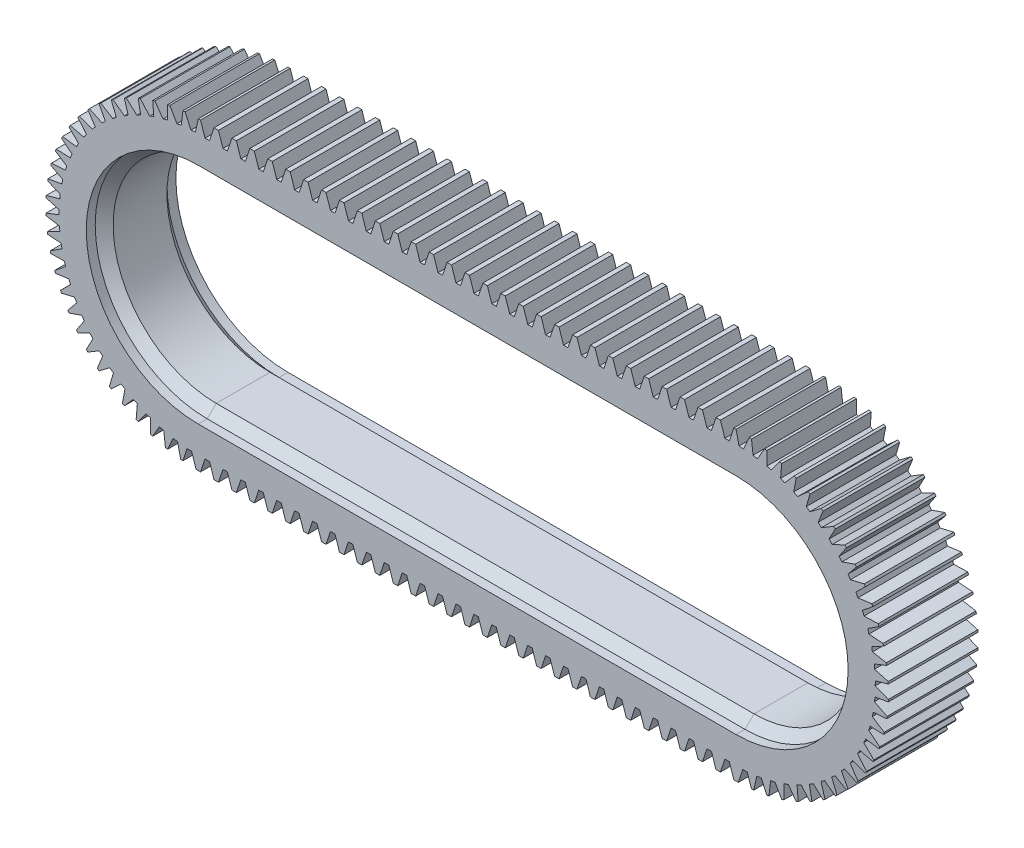
SolidWorks part; units mm, degrees
ref_plane "Ön Düzlem" through (0, 0, 0) normal (0, 0, 1) x (1, 0, 0)
ref_plane "Üst Düzlem" through (0, 0, 0) normal (0, 1, 0) x (1, 0, 0)
ref_plane "Sağ Düzlem" through (0, 0, 0) normal (1, 0, 0) x (0, 0, -1)
sketch "Çizim1" plane through (0, 0, 0) normal (0, 0, 1) x (1, 0, 0)
  line L0 (-26.25, 17) -> (-26, 17)
  line L3 (-30, 0) -> (30, 0) construction
  line L4 (-30, 12.5) -> (30, 12.5)
  line L5 (-30, -12.5) -> (30, -12.5)
  line L6 (-29.999, 17) -> (-29.75, 17)
  line L7 (-29.75, 17) -> (-29.25, 15.5)
  line L8 (-29.25, 15.5) -> (-28.75, 15.5)
  line L9 (-28.75, 15.5) -> (-28.25, 17)
  line L10 (-28.25, 17) -> (-28, 17)
  line L11 (-26.75, 15.5) -> (-26.25, 17)
  line L12 (-27.25, 15.5) -> (-26.75, 15.5)
  line L13 (-27.75, 17) -> (-27.25, 15.5)
  line L14 (-28, 17) -> (-27.75, 17)
  line L15 (-24.25, 17) -> (-24, 17)
  line L16 (-24.75, 15.5) -> (-24.25, 17)
  line L17 (-25.25, 15.5) -> (-24.75, 15.5)
  line L18 (-25.75, 17) -> (-25.25, 15.5)
  line L19 (-26, 17) -> (-25.75, 17)
  line L20 (-22.25, 17) -> (-22, 17)
  line L21 (-22.75, 15.5) -> (-22.25, 17)
  line L22 (-23.25, 15.5) -> (-22.75, 15.5)
  line L23 (-23.75, 17) -> (-23.25, 15.5)
  line L24 (-24, 17) -> (-23.75, 17)
  line L25 (-20.25, 17) -> (-20, 17)
  line L26 (-20.75, 15.5) -> (-20.25, 17)
  line L27 (-21.25, 15.5) -> (-20.75, 15.5)
  line L28 (-21.75, 17) -> (-21.25, 15.5)
  line L29 (-22, 17) -> (-21.75, 17)
  line L30 (-18.25, 17) -> (-18, 17)
  line L31 (-18.75, 15.5) -> (-18.25, 17)
  line L32 (-19.25, 15.5) -> (-18.75, 15.5)
  line L33 (-19.75, 17) -> (-19.25, 15.5)
  line L34 (-20, 17) -> (-19.75, 17)
  line L35 (-16.25, 17) -> (-16, 17)
  line L36 (-16.75, 15.5) -> (-16.25, 17)
  line L37 (-17.25, 15.5) -> (-16.75, 15.5)
  line L38 (-17.75, 17) -> (-17.25, 15.5)
  line L39 (-18, 17) -> (-17.75, 17)
  line L40 (-14.25, 17) -> (-14, 17)
  line L41 (-14.75, 15.5) -> (-14.25, 17)
  line L42 (-15.25, 15.5) -> (-14.75, 15.5)
  line L43 (-15.75, 17) -> (-15.25, 15.5)
  line L44 (-16, 17) -> (-15.75, 17)
  line L45 (-12.25, 17) -> (-12, 17)
  line L46 (-12.75, 15.5) -> (-12.25, 17)
  line L47 (-13.25, 15.5) -> (-12.75, 15.5)
  line L48 (-13.75, 17) -> (-13.25, 15.5)
  line L49 (-14, 17) -> (-13.75, 17)
  line L50 (-10.25, 17) -> (-10, 17)
  line L51 (-10.75, 15.5) -> (-10.25, 17)
  line L52 (-11.25, 15.5) -> (-10.75, 15.5)
  line L53 (-11.75, 17) -> (-11.25, 15.5)
  line L54 (-12, 17) -> (-11.75, 17)
  line L55 (-8.25, 17) -> (-8, 17)
  line L56 (-8.75, 15.5) -> (-8.25, 17)
  line L57 (-9.25, 15.5) -> (-8.75, 15.5)
  line L58 (-9.75, 17) -> (-9.25, 15.5)
  line L59 (-10, 17) -> (-9.75, 17)
  line L60 (-6.25, 17) -> (-6, 17)
  line L61 (-6.75, 15.5) -> (-6.25, 17)
  line L62 (-7.25, 15.5) -> (-6.75, 15.5)
  line L63 (-7.75, 17) -> (-7.25, 15.5)
  line L64 (-8, 17) -> (-7.75, 17)
  line L65 (-4.25, 17) -> (-4, 17)
  line L66 (-4.75, 15.5) -> (-4.25, 17)
  line L67 (-5.25, 15.5) -> (-4.75, 15.5)
  line L68 (-5.75, 17) -> (-5.25, 15.5)
  line L69 (-6, 17) -> (-5.75, 17)
  line L70 (-2.25, 17) -> (-2, 17)
  line L71 (-2.75, 15.5) -> (-2.25, 17)
  line L72 (-3.25, 15.5) -> (-2.75, 15.5)
  line L73 (-3.75, 17) -> (-3.25, 15.5)
  line L74 (-4, 17) -> (-3.75, 17)
  line L75 (-0.25, 17) -> (0, 17)
  line L76 (-0.75, 15.5) -> (-0.25, 17)
  line L77 (-1.25, 15.5) -> (-0.75, 15.5)
  line L78 (-1.75, 17) -> (-1.25, 15.5)
  line L79 (-2, 17) -> (-1.75, 17)
  line L80 (1.75, 17) -> (2, 17)
  line L81 (1.25, 15.5) -> (1.75, 17)
  line L82 (0.75, 15.5) -> (1.25, 15.5)
  line L83 (0.25, 17) -> (0.75, 15.5)
  line L84 (0, 17) -> (0.25, 17)
  line L85 (3.75, 17) -> (4, 17)
  line L86 (3.25, 15.5) -> (3.75, 17)
  line L87 (2.75, 15.5) -> (3.25, 15.5)
  line L88 (2.25, 17) -> (2.75, 15.5)
  line L89 (2, 17) -> (2.25, 17)
  line L90 (5.75, 17) -> (6, 17)
  line L91 (5.25, 15.5) -> (5.75, 17)
  line L92 (4.75, 15.5) -> (5.25, 15.5)
  line L93 (4.25, 17) -> (4.75, 15.5)
  line L94 (4, 17) -> (4.25, 17)
  line L95 (7.75, 17) -> (8, 17)
  line L96 (7.25, 15.5) -> (7.75, 17)
  line L97 (6.75, 15.5) -> (7.25, 15.5)
  line L98 (6.25, 17) -> (6.75, 15.5)
  line L99 (6, 17) -> (6.25, 17)
  line L100 (9.75, 17) -> (10, 17)
  line L101 (9.25, 15.5) -> (9.75, 17)
  line L102 (8.75, 15.5) -> (9.25, 15.5)
  line L103 (8.25, 17) -> (8.75, 15.5)
  line L104 (8, 17) -> (8.25, 17)
  line L105 (11.75, 17) -> (12, 17)
  line L106 (11.25, 15.5) -> (11.75, 17)
  line L107 (10.75, 15.5) -> (11.25, 15.5)
  line L108 (10.25, 17) -> (10.75, 15.5)
  line L109 (10, 17) -> (10.25, 17)
  line L110 (13.75, 17) -> (14, 17)
  line L111 (13.25, 15.5) -> (13.75, 17)
  line L112 (12.75, 15.5) -> (13.25, 15.5)
  line L113 (12.25, 17) -> (12.75, 15.5)
  line L114 (12, 17) -> (12.25, 17)
  line L115 (15.75, 17) -> (16, 17)
  line L116 (15.25, 15.5) -> (15.75, 17)
  line L117 (14.75, 15.5) -> (15.25, 15.5)
  line L118 (14.25, 17) -> (14.75, 15.5)
  line L119 (14, 17) -> (14.25, 17)
  line L120 (17.75, 17) -> (18, 17)
  line L121 (17.25, 15.5) -> (17.75, 17)
  line L122 (16.75, 15.5) -> (17.25, 15.5)
  line L123 (16.25, 17) -> (16.75, 15.5)
  line L124 (16, 17) -> (16.25, 17)
  line L125 (19.75, 17) -> (20, 17)
  line L126 (19.25, 15.5) -> (19.75, 17)
  line L127 (18.75, 15.5) -> (19.25, 15.5)
  line L128 (18.25, 17) -> (18.75, 15.5)
  line L129 (18, 17) -> (18.25, 17)
  line L130 (21.75, 17) -> (22, 17)
  line L131 (21.25, 15.5) -> (21.75, 17)
  line L132 (20.75, 15.5) -> (21.25, 15.5)
  line L133 (20.25, 17) -> (20.75, 15.5)
  line L134 (20, 17) -> (20.25, 17)
  line L135 (23.75, 17) -> (24, 17)
  line L136 (23.25, 15.5) -> (23.75, 17)
  line L137 (22.75, 15.5) -> (23.25, 15.5)
  line L138 (22.25, 17) -> (22.75, 15.5)
  line L139 (22, 17) -> (22.25, 17)
  line L140 (25.75, 17) -> (26, 17)
  line L141 (25.25, 15.5) -> (25.75, 17)
  line L142 (24.75, 15.5) -> (25.25, 15.5)
  line L143 (24.25, 17) -> (24.75, 15.5)
  line L144 (24, 17) -> (24.25, 17)
  line L145 (27.75, 17) -> (28, 17)
  line L146 (27.25, 15.5) -> (27.75, 17)
  line L147 (26.75, 15.5) -> (27.25, 15.5)
  line L148 (26.25, 17) -> (26.75, 15.5)
  line L149 (26, 17) -> (26.25, 17)
  line L150 (29.75, 17) -> (29.999, 17)
  line L151 (29.25, 15.5) -> (29.75, 17)
  line L152 (28.75, 15.5) -> (29.25, 15.5)
  line L153 (28.25, 17) -> (28.75, 15.5)
  line L154 (28, 17) -> (28.25, 17)
  line L155 (-69.9022, 0) -> (58.382, 0) construction
  line L156 (28, -17) -> (28.25, -17)
  line L157 (28.25, -17) -> (28.75, -15.5)
  line L158 (28.75, -15.5) -> (29.25, -15.5)
  line L159 (29.25, -15.5) -> (29.75, -17)
  line L160 (29.75, -17) -> (30, -17)
  line L161 (26, -17) -> (26.25, -17)
  line L162 (26.25, -17) -> (26.75, -15.5)
  line L163 (26.75, -15.5) -> (27.25, -15.5)
  line L164 (27.25, -15.5) -> (27.75, -17)
  line L165 (27.75, -17) -> (28, -17)
  line L166 (24, -17) -> (24.25, -17)
  line L167 (24.25, -17) -> (24.75, -15.5)
  line L168 (24.75, -15.5) -> (25.25, -15.5)
  line L169 (25.25, -15.5) -> (25.75, -17)
  line L170 (25.75, -17) -> (26, -17)
  line L171 (22, -17) -> (22.25, -17)
  line L172 (22.25, -17) -> (22.75, -15.5)
  line L173 (22.75, -15.5) -> (23.25, -15.5)
  line L174 (23.25, -15.5) -> (23.75, -17)
  line L175 (23.75, -17) -> (24, -17)
  line L176 (20, -17) -> (20.25, -17)
  line L177 (20.25, -17) -> (20.75, -15.5)
  line L178 (20.75, -15.5) -> (21.25, -15.5)
  line L179 (21.25, -15.5) -> (21.75, -17)
  line L180 (21.75, -17) -> (22, -17)
  line L181 (18, -17) -> (18.25, -17)
  line L182 (18.25, -17) -> (18.75, -15.5)
  line L183 (18.75, -15.5) -> (19.25, -15.5)
  line L184 (19.25, -15.5) -> (19.75, -17)
  line L185 (19.75, -17) -> (20, -17)
  line L186 (16, -17) -> (16.25, -17)
  line L187 (16.25, -17) -> (16.75, -15.5)
  line L188 (16.75, -15.5) -> (17.25, -15.5)
  line L189 (17.25, -15.5) -> (17.75, -17)
  line L190 (17.75, -17) -> (18, -17)
  line L191 (14, -17) -> (14.25, -17)
  line L192 (14.25, -17) -> (14.75, -15.5)
  line L193 (14.75, -15.5) -> (15.25, -15.5)
  line L194 (15.25, -15.5) -> (15.75, -17)
  line L195 (15.75, -17) -> (16, -17)
  line L196 (12, -17) -> (12.25, -17)
  line L197 (12.25, -17) -> (12.75, -15.5)
  line L198 (12.75, -15.5) -> (13.25, -15.5)
  line L199 (13.25, -15.5) -> (13.75, -17)
  line L200 (13.75, -17) -> (14, -17)
  line L201 (10, -17) -> (10.25, -17)
  line L202 (10.25, -17) -> (10.75, -15.5)
  line L203 (10.75, -15.5) -> (11.25, -15.5)
  line L204 (11.25, -15.5) -> (11.75, -17)
  line L205 (11.75, -17) -> (12, -17)
  line L206 (8, -17) -> (8.25, -17)
  line L207 (8.25, -17) -> (8.75, -15.5)
  line L208 (8.75, -15.5) -> (9.25, -15.5)
  line L209 (9.25, -15.5) -> (9.75, -17)
  line L210 (9.75, -17) -> (10, -17)
  line L211 (6, -17) -> (6.25, -17)
  line L212 (6.25, -17) -> (6.75, -15.5)
  line L213 (6.75, -15.5) -> (7.25, -15.5)
  line L214 (7.25, -15.5) -> (7.75, -17)
  line L215 (7.75, -17) -> (8, -17)
  line L216 (4, -17) -> (4.25, -17)
  line L217 (4.25, -17) -> (4.75, -15.5)
  line L218 (4.75, -15.5) -> (5.25, -15.5)
  line L219 (5.25, -15.5) -> (5.75, -17)
  line L220 (5.75, -17) -> (6, -17)
  line L221 (2, -17) -> (2.25, -17)
  line L222 (2.25, -17) -> (2.75, -15.5)
  line L223 (2.75, -15.5) -> (3.25, -15.5)
  line L224 (3.25, -15.5) -> (3.75, -17)
  line L225 (3.75, -17) -> (4, -17)
  line L226 (0, -17) -> (0.25, -17)
  line L227 (0.25, -17) -> (0.75, -15.5)
  line L228 (0.75, -15.5) -> (1.25, -15.5)
  line L229 (1.25, -15.5) -> (1.75, -17)
  line L230 (1.75, -17) -> (2, -17)
  line L231 (-2, -17) -> (-1.75, -17)
  line L232 (-1.75, -17) -> (-1.25, -15.5)
  line L233 (-1.25, -15.5) -> (-0.75, -15.5)
  line L234 (-0.75, -15.5) -> (-0.25, -17)
  line L235 (-0.25, -17) -> (0, -17)
  line L236 (-4, -17) -> (-3.75, -17)
  line L237 (-3.75, -17) -> (-3.25, -15.5)
  line L238 (-3.25, -15.5) -> (-2.75, -15.5)
  line L239 (-2.75, -15.5) -> (-2.25, -17)
  line L240 (-2.25, -17) -> (-2, -17)
  line L241 (-6, -17) -> (-5.75, -17)
  line L242 (-5.75, -17) -> (-5.25, -15.5)
  line L243 (-5.25, -15.5) -> (-4.75, -15.5)
  line L244 (-4.75, -15.5) -> (-4.25, -17)
  line L245 (-4.25, -17) -> (-4, -17)
  line L246 (-8, -17) -> (-7.75, -17)
  line L247 (-7.75, -17) -> (-7.25, -15.5)
  line L248 (-7.25, -15.5) -> (-6.75, -15.5)
  line L249 (-6.75, -15.5) -> (-6.25, -17)
  line L250 (-6.25, -17) -> (-6, -17)
  line L251 (-10, -17) -> (-9.75, -17)
  line L252 (-9.75, -17) -> (-9.25, -15.5)
  line L253 (-9.25, -15.5) -> (-8.75, -15.5)
  line L254 (-8.75, -15.5) -> (-8.25, -17)
  line L255 (-8.25, -17) -> (-8, -17)
  line L256 (-12, -17) -> (-11.75, -17)
  line L257 (-11.75, -17) -> (-11.25, -15.5)
  line L258 (-11.25, -15.5) -> (-10.75, -15.5)
  line L259 (-10.75, -15.5) -> (-10.25, -17)
  line L260 (-10.25, -17) -> (-10, -17)
  line L261 (-14, -17) -> (-13.75, -17)
  line L262 (-13.75, -17) -> (-13.25, -15.5)
  line L263 (-13.25, -15.5) -> (-12.75, -15.5)
  line L264 (-12.75, -15.5) -> (-12.25, -17)
  line L265 (-12.25, -17) -> (-12, -17)
  line L266 (-16, -17) -> (-15.75, -17)
  line L267 (-15.75, -17) -> (-15.25, -15.5)
  line L268 (-15.25, -15.5) -> (-14.75, -15.5)
  line L269 (-14.75, -15.5) -> (-14.25, -17)
  line L270 (-14.25, -17) -> (-14, -17)
  line L271 (-18, -17) -> (-17.75, -17)
  line L272 (-17.75, -17) -> (-17.25, -15.5)
  line L273 (-17.25, -15.5) -> (-16.75, -15.5)
  line L274 (-16.75, -15.5) -> (-16.25, -17)
  line L275 (-16.25, -17) -> (-16, -17)
  line L276 (-20, -17) -> (-19.75, -17)
  line L277 (-19.75, -17) -> (-19.25, -15.5)
  line L278 (-19.25, -15.5) -> (-18.75, -15.5)
  line L279 (-18.75, -15.5) -> (-18.25, -17)
  line L280 (-18.25, -17) -> (-18, -17)
  line L281 (-22, -17) -> (-21.75, -17)
  line L282 (-21.75, -17) -> (-21.25, -15.5)
  line L283 (-21.25, -15.5) -> (-20.75, -15.5)
  line L284 (-20.75, -15.5) -> (-20.25, -17)
  line L285 (-20.25, -17) -> (-20, -17)
  line L286 (-24, -17) -> (-23.75, -17)
  line L287 (-23.75, -17) -> (-23.25, -15.5)
  line L288 (-23.25, -15.5) -> (-22.75, -15.5)
  line L289 (-22.75, -15.5) -> (-22.25, -17)
  line L290 (-22.25, -17) -> (-22, -17)
  line L291 (-26, -17) -> (-25.75, -17)
  line L292 (-25.75, -17) -> (-25.25, -15.5)
  line L293 (-25.25, -15.5) -> (-24.75, -15.5)
  line L294 (-24.75, -15.5) -> (-24.25, -17)
  line L295 (-24.25, -17) -> (-24, -17)
  line L296 (-28, -17) -> (-27.75, -17)
  line L297 (-27.75, -17) -> (-27.25, -15.5)
  line L298 (-27.25, -15.5) -> (-26.75, -15.5)
  line L299 (-26.75, -15.5) -> (-26.25, -17)
  line L300 (-28.25, -17) -> (-28, -17)
  line L301 (-28.75, -15.5) -> (-28.25, -17)
  line L302 (-29.25, -15.5) -> (-28.75, -15.5)
  line L303 (-29.75, -17) -> (-29.25, -15.5)
  line L304 (-30, -17) -> (-29.75, -17)
  line L305 (-26.25, -17) -> (-26, -17)
  line L306 (30, 0) -> (30, 16.9954) construction
  line L307 (31.4711, 16.9381) -> (31.7188, 16.9129)
  line L308 (30.822, 15.4964) -> (31.4711, 16.9381)
  line L309 (30.3245, 15.5469) -> (30.822, 15.4964)
  line L310 (29.999, 17) -> (30.3245, 15.5469)
  line L312 (33.1772, 16.7023) -> (33.4211, 16.6522)
  line L313 (32.3855, 15.3337) -> (33.1772, 16.7023)
  line L314 (31.8957, 15.4343) -> (32.3855, 15.3337)
  line L315 (31.7188, 16.9129) -> (31.8957, 15.4343)
  line L317 (34.8506, 16.2952) -> (35.0882, 16.2207)
  line L318 (33.9245, 15.0137) -> (34.8506, 16.2952)
  line L319 (33.4475, 15.1634) -> (33.9245, 15.0137)
  line L320 (33.4211, 16.6522) -> (33.4475, 15.1634)
  line L322 (36.4743, 15.7209) -> (36.7031, 15.6227)
  line L323 (35.4233, 14.5396) -> (36.4743, 15.7209)
  line L324 (34.9638, 14.7368) -> (35.4233, 14.5396)
  line L325 (35.0882, 16.2207) -> (34.9638, 14.7368)
  line L327 (38.0315, 14.9852) -> (38.2492, 14.8644)
  line L328 (36.8664, 13.9163) -> (38.0315, 14.9852)
  line L329 (36.4292, 14.159) -> (36.8664, 13.9163)
  line L330 (36.7031, 15.6227) -> (36.4292, 14.159)
  line L332 (39.5064, 14.0958) -> (39.7107, 13.9536)
  line L333 (38.2391, 13.1503) -> (39.5064, 14.0958)
  line L334 (37.8287, 13.4359) -> (38.2391, 13.1503)
  line L335 (38.2492, 14.8644) -> (37.8287, 13.4359)
  line L337 (40.8836, 13.0617) -> (41.0725, 12.8996)
  line L338 (39.5272, 12.2493) -> (40.8836, 13.0617)
  line L339 (39.1478, 12.575) -> (39.5272, 12.2493)
  line L340 (39.7107, 13.9536) -> (39.1478, 12.575)
  line L342 (42.1492, 11.8936) -> (42.3208, 11.7132)
  line L343 (40.7176, 11.2226) -> (42.1492, 11.8936)
  line L344 (40.3731, 11.585) -> (40.7176, 11.2226)
  line L345 (41.0725, 12.8996) -> (40.3731, 11.585)
  line L347 (43.2902, 10.6035) -> (43.4426, 10.4066)
  line L348 (41.7979, 10.0807) -> (43.2902, 10.6035)
  line L349 (41.4919, 10.4761) -> (41.7979, 10.0807)
  line L350 (42.3208, 11.7132) -> (41.4919, 10.4761)
  line L352 (44.2947, 9.2045) -> (44.4264, 8.9933)
  line L353 (42.7573, 8.8354) -> (44.2947, 9.2045)
  line L354 (42.4928, 9.2597) -> (42.7573, 8.8354)
  line L355 (43.4426, 10.4066) -> (42.4928, 9.2597)
  line L357 (45.1526, 7.7112) -> (45.2622, 7.4876)
  line L358 (43.5857, 7.4995) -> (45.1526, 7.7112)
  line L359 (43.3655, 7.9484) -> (43.5857, 7.4995)
  line L360 (44.4264, 8.9933) -> (43.3655, 7.9484)
  line L362 (45.855, 6.1386) -> (45.9414, 5.9052)
  line L363 (44.2747, 6.0865) -> (45.855, 6.1386)
  line L364 (44.101, 6.5554) -> (44.2747, 6.0865)
  line L365 (45.2622, 7.4876) -> (44.101, 6.5554)
  line L367 (46.3946, 4.5031) -> (46.4571, 4.2621)
  line L368 (44.8172, 4.6112) -> (46.3946, 4.5031)
  line L369 (44.6919, 5.0952) -> (44.8172, 4.6112)
  line L370 (45.9414, 5.9052) -> (44.6919, 5.0952)
  line L372 (46.7661, 2.8214) -> (46.8038, 2.5753)
  line L373 (45.2077, 3.0885) -> (46.7661, 2.8214)
  line L374 (45.132, 3.5827) -> (45.2077, 3.0885)
  line L375 (46.4571, 4.2621) -> (45.132, 3.5827)
  line L377 (46.9655, 1.1107) -> (46.9781, 0.8621)
  line L378 (45.4421, 1.5341) -> (46.9655, 1.1107)
  line L379 (45.4168, 2.0335) -> (45.4421, 1.5341)
  line L380 (46.8038, 2.5753) -> (45.4168, 2.0335)
  line L382 (46.9908, -0.6114) -> (46.9782, -0.86)
  line L383 (45.5181, -0.036) -> (46.9908, -0.6114)
  line L384 (45.5434, 0.4633) -> (45.5181, -0.036)
  line L385 (46.9781, 0.8621) -> (45.5434, 0.4633)
  line L387 (46.8418, -2.3272) -> (46.8041, -2.5732)
  line L388 (45.4348, -1.6058) -> (46.8418, -2.3272)
  line L389 (45.5105, -1.1115) -> (45.4348, -1.6058)
  line L390 (46.9782, -0.86) -> (45.5105, -1.1115)
  line L392 (46.52, -4.0191) -> (46.4576, -4.2601)
  line L393 (45.1932, -3.1591) -> (46.52, -4.0191)
  line L394 (45.3185, -2.675) -> (45.1932, -3.1591)
  line L395 (46.8041, -2.5732) -> (45.3185, -2.675)
  line L397 (46.0286, -5.6698) -> (45.9421, -5.9032)
  line L398 (44.7956, -4.6799) -> (46.0286, -5.6698)
  line L399 (44.9693, -4.211) -> (44.7956, -4.6799)
  line L400 (46.4576, -4.2601) -> (44.9693, -4.211)
  line L402 (45.3728, -7.2622) -> (45.2631, -7.4858)
  line L403 (44.2463, -6.1528) -> (45.3728, -7.2622)
  line L404 (44.4665, -5.7039) -> (44.2463, -6.1528)
  line L405 (45.9421, -5.9032) -> (44.4665, -5.7039)
  line L407 (44.5592, -8.7802) -> (44.4275, -8.9915)
  line L408 (43.5507, -7.5625) -> (44.5592, -8.7802)
  line L409 (43.8152, -7.1381) -> (43.5507, -7.5625)
  line L410 (45.2631, -7.4858) -> (43.8152, -7.1381)
  line L412 (43.5962, -10.2081) -> (43.4438, -10.405)
  line L413 (42.7161, -8.8946) -> (43.5962, -10.2081)
  line L414 (43.0222, -8.4992) -> (42.7161, -8.8946)
  line L415 (44.4275, -8.9915) -> (43.0222, -8.4992)
  line L417 (42.4937, -11.5312) -> (42.3222, -11.7117)
  line L418 (41.751, -10.1354) -> (42.4937, -11.5312)
  line L419 (42.0955, -9.773) -> (41.751, -10.1354)
  line L420 (43.4438, -10.405) -> (42.0955, -9.773)
  line L422 (41.263, -12.736) -> (41.0741, -12.8982)
  line L423 (40.6653, -11.2722) -> (41.263, -12.736)
  line L424 (41.0447, -10.9465) -> (40.6653, -11.2722)
  line L425 (42.3222, -11.7117) -> (41.0447, -10.9465)
  line L427 (39.9168, -13.8102) -> (39.7124, -13.9524)
  line L428 (39.4702, -12.2934) -> (39.9168, -13.8102)
  line L429 (39.8806, -12.0077) -> (39.4702, -12.2934)
  line L430 (41.0741, -12.8982) -> (39.8806, -12.0077)
  line L432 (38.4687, -14.7426) -> (38.251, -14.8634)
  line L433 (38.1779, -13.1884) -> (38.4687, -14.7426)
  line L434 (38.6151, -12.9457) -> (38.1779, -13.1884)
  line L435 (39.7124, -13.9524) -> (38.6151, -12.9457)
  line L437 (36.9338, -15.5237) -> (36.705, -15.6219)
  line L438 (36.8017, -13.9481) -> (36.9338, -15.5237)
  line L439 (37.2612, -13.7509) -> (36.8017, -13.9481)
  line L440 (38.251, -14.8634) -> (37.2612, -13.7509)
  line L442 (35.3277, -16.1455) -> (35.0902, -16.2201)
  line L443 (35.3557, -14.5646) -> (35.3277, -16.1455)
  line L444 (35.8328, -14.415) -> (35.3557, -14.5646)
  line L445 (36.705, -15.6219) -> (35.8328, -14.415)
  line L447 (33.667, -16.6017) -> (33.4231, -16.6518)
  line L448 (33.8548, -15.0317) -> (33.667, -16.6017)
  line L449 (34.3445, -14.9311) -> (33.8548, -15.0317)
  line L450 (35.0902, -16.2201) -> (34.3445, -14.9311)
  line L452 (31.9686, -16.8875) -> (31.7209, -16.9127)
  line L453 (32.3143, -15.3446) -> (31.9686, -16.8875)
  line L454 (32.8117, -15.294) -> (32.3143, -15.3446)
  line L455 (33.4231, -16.6518) -> (32.8117, -15.294)
  line L457 (30.25, -17) -> (30, -17)
  line L458 (30.75, -15.5) -> (30.25, -17)
  line L459 (31.25, -15.5) -> (30.75, -15.5)
  line L460 (31.7209, -16.9127) -> (31.25, -15.5)
  line L463 (-30, 0) -> (-30, 16.9954) construction
  line L466 (-31.7209, -16.9127) -> (-31.25, -15.5)
  line L467 (-31.25, -15.5) -> (-30.75, -15.5)
  line L468 (-30.75, -15.5) -> (-30.25, -17)
  line L469 (-30.25, -17) -> (-30, -17)
  line L471 (-33.4231, -16.6518) -> (-32.8117, -15.294)
  line L472 (-32.8117, -15.294) -> (-32.3143, -15.3446)
  line L473 (-32.3143, -15.3446) -> (-31.9686, -16.8875)
  line L474 (-31.9686, -16.8875) -> (-31.7209, -16.9127)
  line L476 (-35.0902, -16.2201) -> (-34.3445, -14.9311)
  line L477 (-34.3445, -14.9311) -> (-33.8548, -15.0317)
  line L478 (-33.8548, -15.0317) -> (-33.667, -16.6017)
  line L479 (-33.667, -16.6017) -> (-33.4231, -16.6518)
  line L481 (-36.705, -15.6219) -> (-35.8328, -14.415)
  line L482 (-35.8328, -14.415) -> (-35.3557, -14.5646)
  line L483 (-35.3557, -14.5646) -> (-35.3277, -16.1455)
  line L484 (-35.3277, -16.1455) -> (-35.0902, -16.2201)
  line L486 (-38.251, -14.8634) -> (-37.2612, -13.7509)
  line L487 (-37.2612, -13.7509) -> (-36.8017, -13.9481)
  line L488 (-36.8017, -13.9481) -> (-36.9338, -15.5237)
  line L489 (-36.9338, -15.5237) -> (-36.705, -15.6219)
  line L491 (-39.7124, -13.9524) -> (-38.6151, -12.9457)
  line L492 (-38.6151, -12.9457) -> (-38.1779, -13.1884)
  line L493 (-38.1779, -13.1884) -> (-38.4687, -14.7426)
  line L494 (-38.4687, -14.7426) -> (-38.251, -14.8634)
  line L496 (-41.0741, -12.8982) -> (-39.8806, -12.0077)
  line L497 (-39.8806, -12.0077) -> (-39.4702, -12.2934)
  line L498 (-39.4702, -12.2934) -> (-39.9168, -13.8102)
  line L499 (-39.9168, -13.8102) -> (-39.7124, -13.9524)
  line L501 (-42.3222, -11.7117) -> (-41.0447, -10.9465)
  line L502 (-41.0447, -10.9465) -> (-40.6653, -11.2722)
  line L503 (-40.6653, -11.2722) -> (-41.263, -12.736)
  line L504 (-41.263, -12.736) -> (-41.0741, -12.8982)
  line L506 (-43.4438, -10.405) -> (-42.0955, -9.773)
  line L507 (-42.0955, -9.773) -> (-41.751, -10.1354)
  line L508 (-41.751, -10.1354) -> (-42.4937, -11.5312)
  line L509 (-42.4937, -11.5312) -> (-42.3222, -11.7117)
  line L511 (-44.4275, -8.9915) -> (-43.0222, -8.4992)
  line L512 (-43.0222, -8.4992) -> (-42.7161, -8.8946)
  line L513 (-42.7161, -8.8946) -> (-43.5962, -10.2081)
  line L514 (-43.5962, -10.2081) -> (-43.4438, -10.405)
  line L516 (-45.2631, -7.4858) -> (-43.8152, -7.1381)
  line L517 (-43.8152, -7.1381) -> (-43.5507, -7.5625)
  line L518 (-43.5507, -7.5625) -> (-44.5592, -8.7802)
  line L519 (-44.5592, -8.7802) -> (-44.4275, -8.9915)
  line L521 (-45.9421, -5.9032) -> (-44.4665, -5.7039)
  line L522 (-44.4665, -5.7039) -> (-44.2463, -6.1528)
  line L523 (-44.2463, -6.1528) -> (-45.3728, -7.2622)
  line L524 (-45.3728, -7.2622) -> (-45.2631, -7.4858)
  line L526 (-46.4576, -4.2601) -> (-44.9693, -4.211)
  line L527 (-44.9693, -4.211) -> (-44.7956, -4.6799)
  line L528 (-44.7956, -4.6799) -> (-46.0286, -5.6698)
  line L529 (-46.0286, -5.6698) -> (-45.9421, -5.9032)
  line L531 (-46.8041, -2.5732) -> (-45.3185, -2.675)
  line L532 (-45.3185, -2.675) -> (-45.1932, -3.1591)
  line L533 (-45.1932, -3.1591) -> (-46.52, -4.0191)
  line L534 (-46.52, -4.0191) -> (-46.4576, -4.2601)
  line L536 (-46.9782, -0.86) -> (-45.5105, -1.1115)
  line L537 (-45.5105, -1.1115) -> (-45.4348, -1.6058)
  line L538 (-45.4348, -1.6058) -> (-46.8418, -2.3272)
  line L539 (-46.8418, -2.3272) -> (-46.8041, -2.5732)
  line L541 (-46.9781, 0.8621) -> (-45.5434, 0.4633)
  line L542 (-45.5434, 0.4633) -> (-45.5181, -0.036)
  line L543 (-45.5181, -0.036) -> (-46.9908, -0.6114)
  line L544 (-46.9908, -0.6114) -> (-46.9782, -0.86)
  line L546 (-46.8038, 2.5753) -> (-45.4168, 2.0335)
  line L547 (-45.4168, 2.0335) -> (-45.4421, 1.5341)
  line L548 (-45.4421, 1.5341) -> (-46.9655, 1.1107)
  line L549 (-46.9655, 1.1107) -> (-46.9781, 0.8621)
  line L551 (-46.4571, 4.2621) -> (-45.132, 3.5827)
  line L552 (-45.132, 3.5827) -> (-45.2077, 3.0885)
  line L553 (-45.2077, 3.0885) -> (-46.7661, 2.8214)
  line L554 (-46.7661, 2.8214) -> (-46.8038, 2.5753)
  line L556 (-45.9414, 5.9052) -> (-44.6919, 5.0952)
  line L557 (-44.6919, 5.0952) -> (-44.8172, 4.6112)
  line L558 (-44.8172, 4.6112) -> (-46.3946, 4.5031)
  line L559 (-46.3946, 4.5031) -> (-46.4571, 4.2621)
  line L561 (-45.2622, 7.4876) -> (-44.101, 6.5554)
  line L562 (-44.101, 6.5554) -> (-44.2747, 6.0865)
  line L563 (-44.2747, 6.0865) -> (-45.855, 6.1386)
  line L564 (-45.855, 6.1386) -> (-45.9414, 5.9052)
  line L566 (-44.4264, 8.9933) -> (-43.3655, 7.9484)
  line L567 (-43.3655, 7.9484) -> (-43.5857, 7.4995)
  line L568 (-43.5857, 7.4995) -> (-45.1526, 7.7112)
  line L569 (-45.1526, 7.7112) -> (-45.2622, 7.4876)
  line L571 (-43.4426, 10.4066) -> (-42.4928, 9.2597)
  line L572 (-42.4928, 9.2597) -> (-42.7573, 8.8354)
  line L573 (-42.7573, 8.8354) -> (-44.2947, 9.2045)
  line L574 (-44.2947, 9.2045) -> (-44.4264, 8.9933)
  line L576 (-42.3208, 11.7132) -> (-41.4919, 10.4761)
  line L577 (-41.4919, 10.4761) -> (-41.7979, 10.0807)
  line L578 (-41.7979, 10.0807) -> (-43.2902, 10.6035)
  line L579 (-43.2902, 10.6035) -> (-43.4426, 10.4066)
  line L581 (-41.0725, 12.8996) -> (-40.3731, 11.585)
  line L582 (-40.3731, 11.585) -> (-40.7176, 11.2226)
  line L583 (-40.7176, 11.2226) -> (-42.1492, 11.8936)
  line L584 (-42.1492, 11.8936) -> (-42.3208, 11.7132)
  line L586 (-39.7107, 13.9536) -> (-39.1478, 12.575)
  line L587 (-39.1478, 12.575) -> (-39.5272, 12.2493)
  line L588 (-39.5272, 12.2493) -> (-40.8836, 13.0617)
  line L589 (-40.8836, 13.0617) -> (-41.0725, 12.8996)
  line L591 (-38.2492, 14.8644) -> (-37.8287, 13.4359)
  line L592 (-37.8287, 13.4359) -> (-38.2391, 13.1503)
  line L593 (-38.2391, 13.1503) -> (-39.5064, 14.0958)
  line L594 (-39.5064, 14.0958) -> (-39.7107, 13.9536)
  line L596 (-36.7031, 15.6227) -> (-36.4292, 14.159)
  line L597 (-36.4292, 14.159) -> (-36.8664, 13.9163)
  line L598 (-36.8664, 13.9163) -> (-38.0315, 14.9852)
  line L599 (-38.0315, 14.9852) -> (-38.2492, 14.8644)
  line L601 (-35.0882, 16.2207) -> (-34.9638, 14.7368)
  line L602 (-34.9638, 14.7368) -> (-35.4233, 14.5396)
  line L603 (-35.4233, 14.5396) -> (-36.4743, 15.7209)
  line L604 (-36.4743, 15.7209) -> (-36.7031, 15.6227)
  line L606 (-33.4211, 16.6522) -> (-33.4475, 15.1634)
  line L607 (-33.4475, 15.1634) -> (-33.9245, 15.0137)
  line L608 (-33.9245, 15.0137) -> (-34.8506, 16.2952)
  line L609 (-34.8506, 16.2952) -> (-35.0882, 16.2207)
  line L611 (-31.7188, 16.9129) -> (-31.8957, 15.4343)
  line L612 (-31.8957, 15.4343) -> (-32.3855, 15.3337)
  line L613 (-32.3855, 15.3337) -> (-33.1772, 16.7023)
  line L614 (-33.1772, 16.7023) -> (-33.4211, 16.6522)
  line L616 (-29.999, 17) -> (-30.3245, 15.5469)
  line L617 (-30.3245, 15.5469) -> (-30.822, 15.4964)
  line L618 (-30.822, 15.4964) -> (-31.4711, 16.9381)
  line L619 (-31.4711, 16.9381) -> (-31.7188, 16.9129)
  line L620 (-27.75, -17) -> (-28, -17)
  line L621 (-29.75, -17) -> (-30, -17)
  line L622 (-29.25, -15.5) -> (-29.75, -17)
  line L623 (-28.75, -15.5) -> (-29.25, -15.5)
  line L624 (-28.25, -17) -> (-28.75, -15.5)
  line L625 (-28, -17) -> (-28.25, -17)
  line L626 (-28, 17) -> (-28.25, 17)
  line L627 (-28.25, 17) -> (-28.75, 15.5)
  line L628 (-28.75, 15.5) -> (-29.25, 15.5)
  line L629 (-29.25, 15.5) -> (-29.75, 17)
  line L630 (-29.75, 17) -> (-29.999, 17)
  line L631 (-27.75, 17) -> (-28, 17)
  line L632 (29.7301, 17.1151) -> (29.9788, 17.0898) [skipped]
  line L633 (31.463, 17.0546) -> (31.7079, 17.0043) [skipped]
  line L634 (33.1809, 16.8191) -> (33.4194, 16.7443) [skipped]
  line L635 (34.8661, 16.411) -> (35.0959, 16.3124) [skipped]
  line L636 (36.5014, 15.8345) -> (36.72, 15.7132) [skipped]
  line L637 (38.07, 15.0955) -> (38.2752, 14.9527) [skipped]
  line L638 (39.5558, 14.2016) -> (39.7455, 14.0388) [skipped]
  line L639 (40.9435, 13.162) -> (41.1158, 12.9808) [skipped]
  line L640 (43.369, 10.6897) -> (43.5013, 10.4775) [skipped]
  line L641 (42.219, 11.9874) -> (42.372, 11.7897) [skipped]
  line L642 (44.3819, 9.2823) -> (44.492, 9.0579) [skipped]
  line L643 (45.2472, 7.7797) -> (45.334, 7.5453) [skipped]
  line L644 (45.956, 6.1972) -> (46.0187, 5.9552) [skipped]
  line L645 (46.5011, 4.5512) -> (46.539, 4.3041) [skipped]
  line L646 (46.8769, 2.8585) -> (46.8895, 2.6088) [skipped]
  line L647 (47.0795, 1.1364) -> (47.0668, 0.8867) [skipped]
  line L648 (47.1068, -0.5973) -> (47.069, -0.8445) [skipped]
  line L649 (46.9586, -2.3249) -> (46.896, -2.567) [skipped]
  line L650 (46.6364, -4.0287) -> (46.5496, -4.2631) [skipped]
  line L651 (46.1435, -5.6911) -> (46.0334, -5.9155) [skipped]
  line L652 (45.4849, -7.2951) -> (45.3526, -7.5073) [skipped]
  line L653 (44.6674, -8.8243) -> (44.5144, -9.0219) [skipped]
  line L654 (43.6994, -10.2629) -> (43.5272, -10.4441) [skipped]
  line L655 (42.5908, -11.5961) -> (42.4012, -11.759) [skipped]
  line L656 (41.3531, -12.8104) -> (41.1479, -12.9533) [skipped]
  line L657 (39.9988, -13.8933) -> (39.7802, -14.0146) [skipped]
  line L658 (38.542, -14.8336) -> (38.3122, -14.9322) [skipped]
  line L659 (36.9975, -15.6216) -> (36.7589, -15.6965) [skipped]
  line L660 (35.3811, -16.2494) -> (35.1363, -16.2997) [skipped]
  line L661 (32, -17) -> (31.75, -17) [skipped]
  line L662 (33.7096, -16.7104) -> (33.4609, -16.7357) [skipped]
  arc A2 (-30, 12.5) -> (-30, -12.5) centre (-30, 0) ccw
  arc A3 (30, -12.5) -> (30, 12.5) centre (30, 0) ccw
  point P10 (0, 0)
  point P505 (30, 0)
  point P692 (-30, 0)
  dimension "D2" = 17
  dimension "D3" = 30
  dimension "D5" = 25
  dimension "D7" = 0.25
  dimension "D8" = 0.5
  dimension "D9" = 0.5
  dimension "D10" = 0.5
  dimension "D11" = 1.5
  dimension "D12" = 32
extrude "Yükseklik-Ekstrüzyon1" add sketch "Çizim1" along normal blind 10 contours L618 L619 L611 L612 L613 L614 L606 L607 L608 L609 L601 L602 L603 L604 L596 L597 L598 L599 L591 L592 L593 L594 L586 L587 L588 L589 L581 L582 L583 L584 L576 L577 L578 L579 L571 L572 L573 L574 L566 L567 L568 L569 L561 L562 L563 L564 L556 L557 L558 L559 L551 region at (-26.125, 16.0006, 0)
ref_plane "Düzlem1" through (0, 0, 5) normal (0, 0, -1) x (-1, 0, 0)
sketch "Çizim2" plane through (0, 0, 5) normal (0, 0, -1) x (-1, 0, 0)
  line L0 (-30, 0) -> (30, 0) construction
  line L3 (-30, 12.5) -> (30, 12.5)
  line L6 (-30, -12.5) -> (30, -12.5)
  line L7 (-30, 0) -> (30, 0) construction
  line L8 (-30, 11.5) -> (30, 11.5)
  line L9 (-30, -11.5) -> (30, -11.5)
  arc A4 (-30, 12.5) -> (-30, -12.5) centre (-30, 0) ccw
  arc A5 (30, -12.5) -> (30, 12.5) centre (30, 0) ccw
  arc A6 (-30, 11.5) -> (-30, -11.5) centre (-30, 0) ccw
  arc A7 (30, -11.5) -> (30, 11.5) centre (30, 0) ccw
  point P4 (0, 0)
  point P9 (0, 0)
  dimension "D1" = 25
  dimension "D2" = 23
extrude "Yükseklik-Ekstrüzyon2" add sketch "Çizim2" along normal blind 3 and the other way blind 3
chamfer "Pah1" distance 1 angle 45 8 edges at (0, 12.5, 2) (42.5, 0, 2) (-42.5, 0, 2) (0, -12.5, 2) (0, -12.5, 8) (-42.5, 0, 8) (42.5, 0, 8) (0, 12.5, 8)
